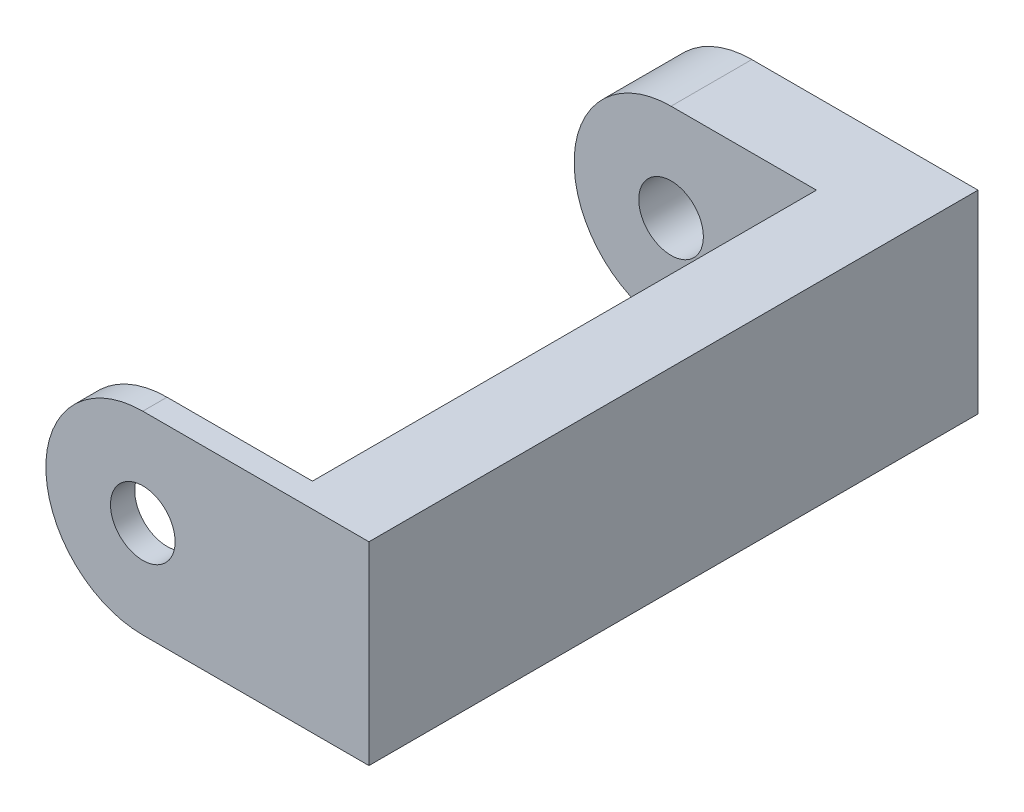
SolidWorks part; units mm, degrees
ref_plane "Front Plane" through (0, 0, 0) normal (0, 0, 1) x (1, 0, 0)
ref_plane "Top Plane" through (0, 0, 0) normal (0, 1, 0) x (1, 0, 0)
ref_plane "Right Plane" through (0, 0, 0) normal (1, 0, 0) x (0, 0, -1)
sketch "Sketch2" plane through (0, 0, 0) normal (0, 0, 1) x (1, 0, 0)
  line L2 (0, -12) -> (28, -12)
  line L4 (0, 12) -> (28, 12)
  line L5 (28, -12) -> (28, 12)
  arc A1 (0, 12) -> (0, -12) centre (0, 0) ccw
extrude "Boss-Extrude3" add sketch "Sketch2" along normal blind 75.4 contours L4 A1 L2 L5 region at (9.1918, 0, 0)
sketch "Sketch3" plane through (0, -12, 0) normal (0, -1, 0) x (1, 0, 0)
  line L0 (28, 75.4) -> (28, 0) construction
  line L1 (18, 10) -> (-22.6636, 10)
  line L2 (18, 10) -> (18, 72.4)
  line L3 (18, 72.4) -> (-22.6636, 72.4)
  line L4 (-22.6636, 10) -> (-22.6636, 72.4)
  line L5 (0, 75.4) -> (28, 75.4) construction
  line L6 (0, 0) -> (28, 0) construction
  dimension "D1" = 10
  dimension "D2" = 3
  dimension "D3" = 10
extrude "Cut-Extrude1" cut sketch "Sketch3" against normal blind 75.4
hole_wizard "Ø8.0mm Dowel Hole2" positions "Sketch4" profile "Sketch6" hole size "Ø8.0" standard "ISO"
sketch "Sketch4" plane through (0, 0, 75.4) normal (0, 0, 1) x (1, 0, 0)
  point P0 (0, 0)
sketch "Sketch6" plane through (0, 0, 75.4) normal (1, 0, 0) x (0, -1, 0)
  line L0 (0, 0) -> (0, 5.4034)
  line L1 (0, 5.4034) -> (4, 3)
  line L2 (4, 3) -> (4, 0)
  line L5 (4, 0) -> (0, 0)
  line L10 (0, 5.4034) -> (-4, 3) construction
  line L11 (0, -6.35) -> (0, 107.95) construction
  dimension "Hole Dia." = 8
  dimension "Hole Depth" = 3
  dimension "Drill Angle" = 118
hole_wizard "Ø8.0mm Dowel Hole1" positions "Sketch7" profile "Sketch9" hole size "Ø8.0" standard "ISO" end condition through all
sketch "Sketch7" plane through (0, 0, 10) normal (0, 0, 1) x (1, 0, 0)
  point P0 (0, 0)
sketch "Sketch9" plane through (0, 0, 10) normal (1, 0, 0) x (0, -1, 0)
  line L0 (0, 0) -> (0, 10)
  line L1 (0, 10) -> (4, 10)
  line L2 (4, 10) -> (4, 0)
  line L5 (4, 0) -> (0, 0)
  line L11 (0, -6.35) -> (0, 107.95) construction
  dimension "Thru Hole Dia." = 8
  dimension "Thru Hole Depth" = 10
